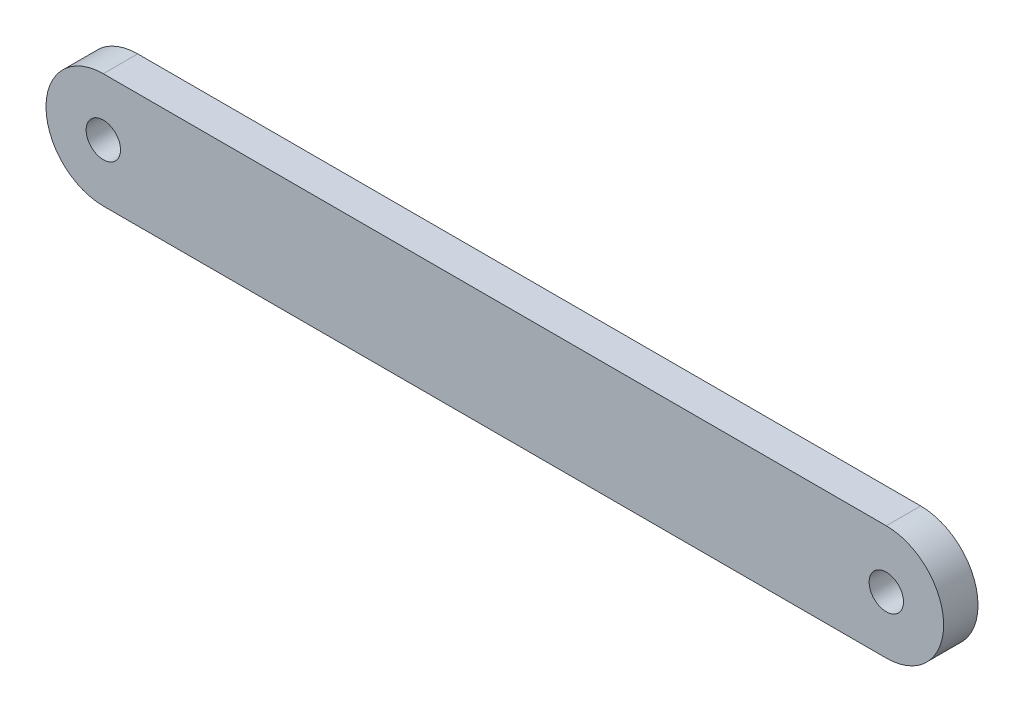
SolidWorks part; units mm, degrees
ref_plane "前基準面" through (0, 0, 0) normal (0, 0, 1) x (1, 0, 0)
ref_plane "上基準面" through (0, 0, 0) normal (0, 1, 0) x (1, 0, 0)
ref_plane "右基準面" through (0, 0, 0) normal (1, 0, 0) x (0, 0, -1)
sketch "草圖1" plane through (0, 0, 0) normal (0, 0, 1) x (1, 0, 0)
  line L0 (-17.08, 0) -> (17.08, 0) construction
  line L1 (-17.08, 2.5) -> (17.08, 2.5)
  line L2 (-17.08, -2.5) -> (17.08, -2.5)
  arc A0 (-17.08, 2.5) -> (-17.08, -2.5) centre (-17.08, 0) ccw
  arc A1 (17.08, -2.5) -> (17.08, 2.5) centre (17.08, 0) ccw
  circle A2 centre (-17.08, 0) radius 0.75
  circle A3 centre (17.08, 0) radius 0.75
  point P3 (0, 0)
  dimension "D2" = 2.5
  dimension "D3" = 1.5
  dimension "D1" = 34.16
extrude "填料-伸長1" add sketch "草圖1" along normal mid plane 1.5
